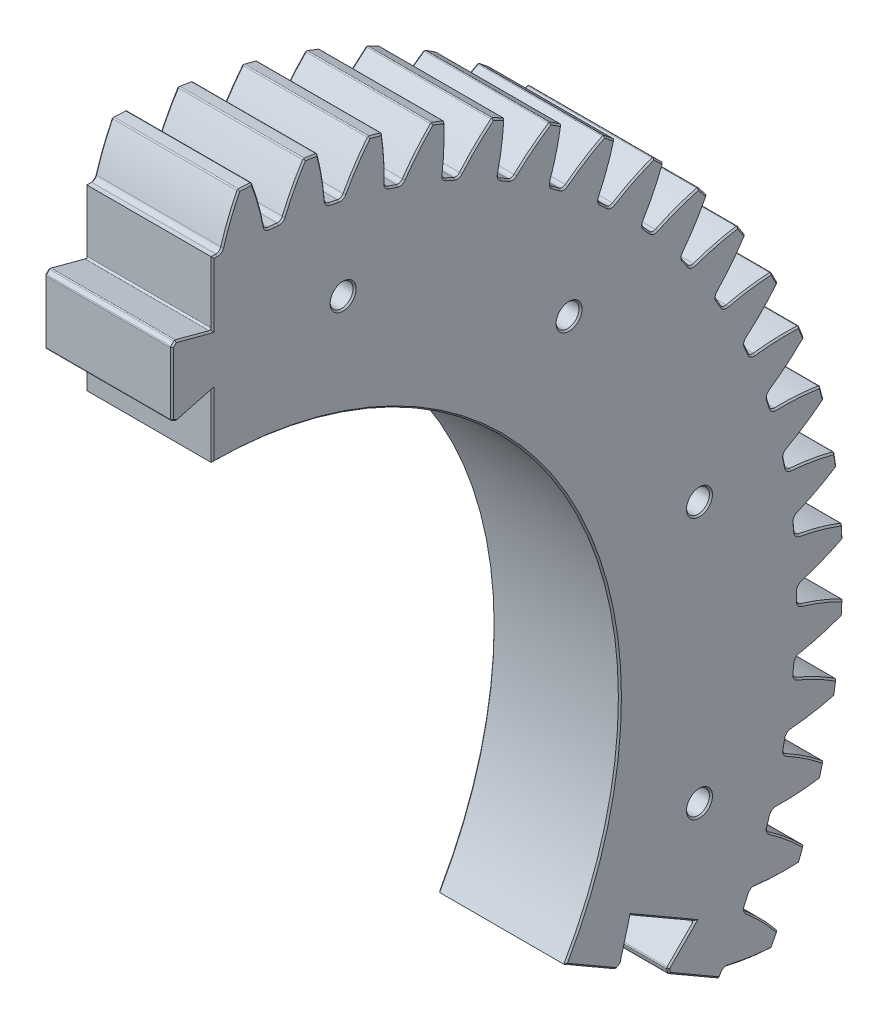
SolidWorks part; units mm, degrees
ref_plane "Plane1" through (0, 0, 0) normal (0, 0, 1) x (1, 0, 0)
ref_plane "Plane2" through (0, 0, 0) normal (0, 1, 0) x (1, 0, 0)
ref_plane "Plane3" through (0, 0, 0) normal (1, 0, 0) x (0, 0, -1)
sketch "HoldingSke" plane through (0, 0, 0) normal (0, 1, 0) x (1, 0, 0)
  line L0 (0, 0) -> (0.125, -0.2165)
  line L1 (-15, 0) -> (100, 0) construction
  line L2 (0, 0) -> (-2.1039, 2.3779)
  line L3 (0, 0) -> (-11.863, 4.5341)
  line L4 (0, 0) -> (4.318, 7.479)
  line L5 (0, 0) -> (-46.8476, -17.4728)
  line L6 (0, 0) -> (-20.7241, -13.9826)
  line L7 (-2.1039, 2.3779) -> (8.6586, 51.2059)
  line L8 (-76.2, 54.61) -> (-66.8, 54.61)
  line L9 (-71.009, 38.7566) -> (-53.1078, 45.2721)
  line L10 (-76.2, 71.12) -> (104.1128, 71.12)
  line L11 (0, 0) -> (-25, 0)
  line L12 (-76.2, 101.6) -> (-76.073, 101.6)
  line L13 (24.9733, 27.94) -> (52.9518, 28.4284)
  line L14 (24.9733, 27.94) -> (24.9743, 27.94)
  line L15 (24.9733, 27.94) -> (100.4006, 29.5858)
  line L16 (-63.627, -4) -> (-12.827, -4)
  circle A0 centre (0, 0) radius 80
  circle A1 centre (0, 0) radius 37.5
  circle A2 centre (0, 0) radius 37.5
  circle A3 centre (0, 0) radius 80
  dimension "Num_teeth" = 60
  dimension "Pitch_radius" = 180.3128
  dimension "Width" = 25
  dimension "Thickness" = 25
sketch "BasProSke" plane through (0, 0, 0) normal (0, 1, 0) x (1, 0, 0)
  line L0 (-10, 0) -> (60, 0) construction
  line L1 (0, 0) -> (0, 124)
  line L2 (0, 0) -> (25, 0)
  line L3 (25, 0) -> (25, 124)
  line L4 (25, 124) -> (0, 124)
  dimension "Thickness" = 25
  dimension "Diameter" = 248
revolve "Base-Revolve" add sketch "BasProSke" angle 360 about L0
sketch "TooCutSke" plane through (0, 0, 0) normal (1, 0, 0) x (0, 0, -1)
  line L1 (0, 0) -> (0, 107) construction
  line L2 (0, 0) -> (-3.3635, 119.9529) construction
  line L3 (0, 0) -> (-12.5569, 239.6002) construction
  line L4 (-3.3635, 119.9529) -> (-6.2785, 119.8001) construction
  arc A0 (1.6795, 114.9867) -> (-1.6795, 114.9867) centre (0, 0) ccw
  arc A1 (5.1673, 123.9177) -> (-5.1673, 123.9177) centre (0, 0) ccw
  circle A2 centre (0, 0) radius 120 construction
  circle A3 centre (0, 0) radius 112.7631 construction
  arc A4 (-1.6795, 114.9867) -> (-5.1673, 123.9177) centre (-47.9113, 102.0785) ccw
  arc A5 (5.1673, 123.9177) -> (1.6795, 114.9867) centre (47.9113, 102.0785) ccw
extrude "ToothCut" cut sketch "TooCutSke" along normal through all
fillet "Breaks" [suppressed] radius 0.08
fillet "RootFillets" [suppressed] radius 1.001
pattern_circular "TeethCuts" count 60 every 6 about axis through (-10, 0, 0) along (1, 0, 0) of "ToothCut", "RootFillets", "Breaks"
sketch "HubNeaOneSke" plane through (0, 0, 0) normal (-1, 0, 0) x (0, 0, 1)
  circle A0 centre (0, 0) radius 37.5
  dimension "Diameter" = 75
extrude "HubNearOne" [suppressed] add sketch "HubNeaOneSke" along normal blind 25.0001
sketch "HubNeaBotSke" plane through (0, 0, 0) normal (-1, 0, 0) x (0, 0, 1)
  circle A0 centre (0, 0) radius 37.5
  dimension "Diameter" = 75
extrude "HubNearBoth" [suppressed] add sketch "HubNeaBotSke" along normal blind 12.5
ref_plane "FarPln" through (25, 0, 0) normal (1, 0, 0) x (0, 0, -1)
sketch "HubFarSke" plane through (25, 0, 0) normal (1, 0, 0) x (0, 0, -1)
  circle A0 centre (0, 0) radius 37.5
  dimension "Diameter" = 75
extrude "HubFar" [suppressed] add sketch "HubFarSke" along normal blind 12.5
sketch "BorSke" plane through (0, 0, 0) normal (1, 0, 0) x (0, 0, -1)
  circle A0 centre (0, 0) radius 80
  dimension "Diameter" = 160
extrude "Bore" cut sketch "BorSke" along normal mid plane 100.0001
sketch "KeySke" plane through (0, 0, 0) normal (1, 0, 0) x (0, 0, -1)
  line L0 (-20, 0) -> (-20, 89.4)
  line L1 (-20, 89.4) -> (20, 89.4)
  line L2 (20, 89.4) -> (20, 0)
  line L3 (0, 0) -> (0, 34) construction
  line L4 (-20, 0) -> (20, 0)
  dimension "Width" = 40
extrude "Keyway" [suppressed] cut sketch "KeySke" along normal mid plane 100.0001
pattern_circular "Keyway2" [suppressed] count 2 every 90 about axis through (-10, 0, 0) along (1, 0, 0)
sketch "Esquisse2" plane through (25, 0, 0) normal (1, 0, 0) x (0, 0, -1)
  line L0 (0, 0) -> (0, 145.329) construction
  line L1 (0, 0) -> (-133.1237, -76.859) construction
  line L2 (0, 0) -> (160.6659, -92.7605) construction
  line L3 (0, 114.999) -> (0, 102.5)
  line L4 (0, 102.5) -> (-8, 104.6436)
  line L5 (-8, 104.6436) -> (-8, 90.3564)
  line L6 (-8, 90.3564) -> (0, 92.5)
  line L10 (0, 0) -> (80.0207, -46.2)
  line L11 (80.0207, -46.2) -> (82.2045, -38.05)
  line L12 (82.2045, -38.05) -> (94.8204, -45.3338)
  line L13 (94.8204, -45.3338) -> (88.8542, -51.3)
  line L14 (88.8542, -51.3) -> (114.7231, -66.2354)
  line L15 (114.7231, -66.2354) -> (38.3008, -156.6616)
  line L16 (38.3008, -156.6616) -> (-106.3416, -136.6523)
  line L17 (-106.3416, -136.6523) -> (-159.8958, -12.4772)
  line L18 (-159.8958, -12.4772) -> (-109.243, 114.999)
  line L19 (-109.243, 114.999) -> (0, 136.3991)
  line L20 (0, 136.3991) -> (0, 114.999)
  line L21 (0, 92.5) -> (0, 0)
  arc A0 (1.6795, 114.9867) -> (-1.6795, 114.9867) centre (0, 0) ccw construction
  dimension "D12" = 8
  dimension "D1" = 120
  dimension "D2" = 120
  dimension "D3" = 75
  dimension "D4" = 92.5
  dimension "D5" = 10
  dimension "D6" = 75
  dimension "D7" = 10.2
  dimension "D8" = 75
  dimension "D9" = 75
  dimension "D10" = 8.15
  dimension "D11" = 92.4
extrude "Enlèv. mat.-Extru.1" cut sketch "Esquisse2" against normal through all
sketch "Esquisse3" plane through (25, 0, 0) normal (1, 0, 0) x (0, 0, -1)
  line L0 (25.6231, 95.6267) -> (0, 0) construction
  line L1 (0, 0) -> (70.0036, 70.0036) construction
  line L2 (95.6267, 25.6231) -> (0, 0) construction
  line L3 (0, 0) -> (95.6267, -25.6231) construction
  line L7 (0, 80) -> (0, 92.5) construction
  circle A1 centre (25.6231, 95.6267) radius 2.25
  circle A2 centre (70.0036, 70.0036) radius 2.25
  circle A3 centre (95.6267, 25.6231) radius 2.25
  circle A4 centre (95.6267, -25.6231) radius 2.25
  arc A6 (69.282, -40) -> (0, 80) centre (0, 0) ccw construction
  dimension "D1" = 4.5
  dimension "D2" = 4.5
  dimension "D3" = 4.5
  dimension "D4" = 4.5
  dimension "D5" = 99
  dimension "D6" = 99
  dimension "D7" = 99
  dimension "D8" = 99
  dimension "D9" = 30
  dimension "D10" = 30
  dimension "D11" = 30
  dimension "D12" = 15
extrude "Enlèv. mat.-Extru.2" cut sketch "Esquisse3" against normal through all
fillet "Congé1" radius 1 40 edges at (12.5, 114.9867, -1.6795) (12.5, 114.5324, -10.3491) (12.5, 114.1813, -13.6897) (12.5, 112.8232, -22.2643) (12.5, 112.1248, -25.5499) (12.5, 109.8779, -33.9355) (12.5, 108.8399, -37.1302) (12.5, 105.7287, -45.235) (12.5, 104.3625, -48.3036) (12.5, 100.4212, -56.0389) (12.5, 98.7417, -58.9479) (12.5, 94.0134, -66.2288) (12.5, 92.039, -68.9463) (12.5, 86.5756, -75.693) (12.5, 84.328, -78.1893) (12.5, 78.1893, -84.328) (12.5, 75.693, -86.5756) (12.5, 68.9463, -92.039) (12.5, 66.2288, -94.0134) (12.5, 58.9479, -98.7417) (12.5, 56.0389, -100.4212) (12.5, 48.3036, -104.3625) (12.5, 45.235, -105.7287) (12.5, 37.1302, -108.8399) (12.5, 33.9355, -109.8779) (12.5, 25.5499, -112.1248) (12.5, 22.2643, -112.8232) (12.5, 13.6897, -114.1813) (12.5, 10.3491, -114.5324) (12.5, 1.6795, -114.9867) (12.5, -1.6795, -114.9867) (12.5, -10.3491, -114.5324) (12.5, -13.6897, -114.1813) (12.5, -22.2643, -112.8232) (12.5, -25.5499, -112.1248) (12.5, -33.9355, -109.8779) (12.5, -37.1302, -108.8399) (12.5, -56.0389, -100.4212) (12.5, -45.235, -105.7287) (12.5, -48.3036, -104.3625)
chamfer "Chanfrein1" distance 0.3 angle 45 272 edges at (25, 86.25, 0) (25, 91.4282, 4) (25, 97.5, 8) (25, 103.5718, 4) (25, 108.7495, 0) (25, 114.9981, -0.4606) (25, 115.1916, -1.5242) (25, 119.8771, -3.3332) (25, 123.8301, -6.4897) (25, 119.5689, -9.2157) (25, 114.7199, -10.5249) (25, 114.369, -12.0207) (25, 114.4013, -13.5567) (25, 118.872, -15.8455) (25, 122.4734, -19.3979) (25, 117.9505, -21.6635) (25, 112.9913, -22.4588) (25, 112.486, -23.9096) (25, 112.3575, -25.4406) (25, 116.5645, -28.1842) (25, 119.7748, -32.0936) (25, 115.0399, -33.874) (25, 110.0248, -34.1465) (25, 109.3705, -35.5366) (25, 109.0827, -37.0458) (25, 112.9799, -40.2141) (25, 115.764, -44.4376) (25, 110.8689, -45.7134) (25, 105.8528, -45.4602) (25, 105.0568, -46.7743) (25, 104.6128, -48.2451) (25, 108.1575, -51.8034) (25, 110.4848, -56.2948) (25, 105.4832, -57.052) (25, 100.521, -56.2758) (25, 99.5921, -57.4995) (25, 98.9968, -58.9158) (25, 102.1501, -62.8252) (25, 103.9952, -67.5352) (25, 98.9418, -67.7654) (25, 94.0879, -66.4748) (25, 93.0361, -67.5947) (25, 92.2961, -68.9411) (25, 95.0235, -73.1586) (25, 96.3661, -78.0357) (25, 91.3164, -77.7364) (25, 86.624, -75.9455) (25, 85.4609, -76.9494) (25, 84.5842, -78.211) (25, 86.8558, -82.6905) (25, 87.6812, -87.6812) (25, 82.6905, -86.8558) (25, 78.211, -84.5842) (25, 76.9494, -85.4609) (25, 75.9455, -86.624) (25, 77.7364, -91.3164) (25, 78.0357, -96.3661) (25, 73.1586, -95.0235) (25, 68.9411, -92.2961) (25, 67.5947, -93.0361) (25, 66.4748, -94.0879) (25, 67.7654, -98.9418) (25, 67.5352, -103.9952) (25, 62.8252, -102.1501) (25, 58.9158, -98.9968) (25, 57.4995, -99.5921) (25, 56.2758, -100.521) (25, 57.052, -105.4832) (25, 56.2948, -110.4848) (25, 51.8034, -108.1575) (25, 48.2451, -104.6128) (25, 46.7743, -105.0568) (25, 45.4602, -105.8528) (25, 45.7134, -110.8689) (25, 44.4376, -115.764) (25, 40.2141, -112.9799) (25, 37.0458, -109.0827) (25, 35.5366, -109.3705) (25, 34.1465, -110.0248) (25, 33.874, -115.0399) (25, 32.0936, -119.7748) (25, 28.1842, -116.5645) (25, 25.4406, -112.3575) (25, 23.9096, -112.486) (25, 22.4588, -112.9913) (25, 21.6635, -117.9505) (25, 19.3979, -122.4734) (25, 15.8455, -118.872) (25, 13.5567, -114.4013) (25, 12.0207, -114.369) (25, 10.5249, -114.7199) (25, 9.2157, -119.5689) (25, 6.4897, -123.8301) (25, 3.3332, -119.8771) (25, 1.5242, -115.1916) (25, 0, -114.999) (25, -1.5242, -115.1916) (25, -3.3332, -119.8771) (25, -6.4897, -123.8301) (25, -9.2157, -119.5689) (25, -10.5249, -114.7199) (25, -12.0207, -114.369) (25, -13.5567, -114.4013) (25, -15.8455, -118.872) (25, -19.3979, -122.4734) (25, -21.6635, -117.9505) (25, -22.4588, -112.9913) (25, -23.9096, -112.486) (25, -25.4406, -112.3575) (25, -28.1842, -116.5645) (25, -32.0936, -119.7748) (25, -33.874, -115.0399) (25, -34.1465, -110.0248) (25, -35.5366, -109.3705) (25, -37.0458, -109.0827) (25, -40.2141, -112.9799) (25, -44.4376, -115.764) (25, -45.7134, -110.8689) (25, -45.4602, -105.8528) (25, -46.7743, -105.0568) (25, -48.2451, -104.6128) (25, -51.8034, -108.1575) (25, -56.2948, -110.4848) (25, -57.052, -105.4832) (25, -56.2758, -100.521) (25, -57.1002, -99.8215) (25, -54.3998, -94.2231) (25, -48.3169, -91.8373) (25, -41.6919, -88.5125) (25, -42.125, -81.1126) (25, -43.1, -74.6514) (25, 40, -69.282) (25, -25.6231, -97.8767) (25, 25.6231, -97.8767) (25, 70.0036, -72.2536) (25, 95.6267, -27.8731) (0, -41.6919, -88.5125) (0, -48.3169, -91.8373) (0, -54.3998, -94.2231) (0, -57.1002, -99.8215) (0, -56.2758, -100.521) (0, -57.052, -105.4832) (0, -56.2948, -110.4848) (0, -51.8034, -108.1575) (0, -48.2451, -104.6128) (0, -46.7743, -105.0568) (0, -45.4602, -105.8528) (0, -45.7134, -110.8689) (0, -44.4376, -115.764) (0, -40.2141, -112.9799) (0, -37.0458, -109.0827) (0, -35.5366, -109.3705) (0, -34.1465, -110.0248) (0, -33.874, -115.0399) (0, -32.0936, -119.7748) (0, -28.1842, -116.5645) (0, -25.4406, -112.3575) (0, -23.9096, -112.486) (0, -22.4588, -112.9913) (0, -21.6635, -117.9505) (0, -19.3979, -122.4734) (0, -15.8455, -118.872) (0, -13.5567, -114.4013) (0, -12.0207, -114.369) (0, -10.5249, -114.7199) (0, -9.2157, -119.5689) (0, -6.4897, -123.8301) (0, -3.3332, -119.8771) (0, -1.5242, -115.1916) (0, 0, -114.999) (0, 1.5242, -115.1916) (0, 3.3332, -119.8771) (0, 6.4897, -123.8301) (0, 9.2157, -119.5689) (0, 10.5249, -114.7199) (0, 12.0207, -114.369) (0, 13.5567, -114.4013) (0, 15.8455, -118.872) (0, 19.3979, -122.4734) (0, 21.6635, -117.9505) (0, 22.4588, -112.9913) (0, 23.9096, -112.486) (0, 25.4406, -112.3575) (0, 28.1842, -116.5645) (0, 32.0936, -119.7748) (0, 33.874, -115.0399) (0, 34.1465, -110.0248) (0, 35.5366, -109.3705) (0, 37.0458, -109.0827) (0, 40.2141, -112.9799) (0, 44.4376, -115.764) (0, 45.7134, -110.8689) (0, 45.4602, -105.8528) (0, 46.7743, -105.0568) (0, 48.2451, -104.6128) (0, 51.8034, -108.1575) (0, 56.2948, -110.4848) (0, 57.052, -105.4832) (0, 56.2758, -100.521) (0, 57.4995, -99.5921) (0, 58.9158, -98.9968) (0, 62.8252, -102.1501) (0, 67.5352, -103.9952) (0, 67.7654, -98.9418) (0, 66.4748, -94.0879) (0, 67.5947, -93.0361) (0, 68.9411, -92.2961) (0, 73.1586, -95.0235) (0, 78.0357, -96.3661) (0, 77.7364, -91.3164) (0, 75.9455, -86.624) (0, 76.9494, -85.4609) (0, 78.211, -84.5842) (0, 82.6905, -86.8558) (0, 87.6812, -87.6812) (0, 86.8558, -82.6905) (0, 84.5842, -78.211) (0, 85.4609, -76.9494) (0, 86.624, -75.9455) (0, 91.3164, -77.7364) (0, 96.3661, -78.0357) (0, 95.0235, -73.1586) (0, 92.2961, -68.9411) (0, 93.0361, -67.5947) (0, 94.0879, -66.4748) (0, 98.9418, -67.7654) (0, 103.9952, -67.5352) (0, 102.1501, -62.8252) (0, 98.9968, -58.9158) (0, 99.5921, -57.4995) (0, 100.521, -56.2758) (0, 105.4832, -57.052) (0, 110.4848, -56.2948) (0, 108.1575, -51.8034) (0, 104.6128, -48.2451) (0, 105.0568, -46.7743) (0, 105.8528, -45.4602) (0, 110.8689, -45.7134) (0, 115.764, -44.4376) (0, 112.9799, -40.2141) (0, 109.0827, -37.0458) (0, 109.3705, -35.5366) (0, 110.0248, -34.1465) (0, 115.0399, -33.874) (0, 119.7748, -32.0936) (0, 116.5645, -28.1842) (0, 112.3575, -25.4406) (0, 112.486, -23.9096) (0, 112.9913, -22.4588) (0, 117.9505, -21.6635) (0, 122.4734, -19.3979) (0, 118.872, -15.8455) (0, 114.4013, -13.5567) (0, 114.369, -12.0207) (0, 114.7199, -10.5249) (0, 119.5689, -9.2157) (0, 123.8301, -6.4897) (0, 119.8771, -3.3332) (0, 115.1916, -1.5242) (0, 114.9981, -0.4606) (0, 108.7495, 0) (0, 103.5718, 4) (0, 97.5, 8) (0, 91.4282, 4) (0, 86.25, 0) (0, 40, -69.282) (0, -43.1, -74.6514) (0, -42.125, -81.1126) (0, -25.6231, -97.8767) (0, 25.6231, -97.8767) (0, 70.0036, -72.2536) (0, 95.6267, -27.8731)
sketch "Esquisse4" plane through (0, 0, 0) normal (-1, 0, 0) x (0, 0, 1)
  circle A0 centre (-95.6267, -25.6231) radius 6.75
  circle A1 centre (-95.6267, 25.6231) radius 6.75
  circle A2 centre (-70.0036, 70.0036) radius 6.75
  circle A3 centre (-25.6231, 95.6267) radius 6.75
  dimension "D1" = 13.5
  dimension "D2" = 13.5
  dimension "D3" = 13.5
  dimension "D4" = 13.5
extrude "Enlèv. mat.-Extru.3" cut sketch "Esquisse4" against normal blind 5.2
chamfer "Chanfrein2" distance 0.3 angle 45 4 edges at (0, 95.6267, -18.8731) (0, 70.0036, -63.2536) (0, 25.6231, -88.8767) (0, -25.6231, -88.8767)
chamfer "Chanfrein3" distance 1 angle 45 4 edges at (12.5, -46.2, -80.0207) (12.5, -51.3, -88.8542) (12.5, 90.3564, 8) (12.5, 104.6436, 8)
fillet "Congé2" radius 0.3 12 edges at (12.5, -45.7918, -79.3136) (12.5, -45.2341, -80.2796) (12.5, -38.05, -82.2045) (12.5, -45.3338, -94.8204) (12.5, -50.7226, -89.4316) (12.5, -51.8, -89.7202) (12.5, 104.4323, 7.2113) (12.5, 103.6436, 8) (12.5, 91.1729, 8) (12.5, 90.6152, 7.0341) (12.5, 92.5, 0) (12.5, 102.5, 0)
chamfer "Chanfrein4" distance 0.3 angle 45 8 edges at (0, -51.2237, -89.5658) (25, -51.2237, -89.5658) (0, -45.5324, -79.7629) (25, -45.5324, -79.7629) (25, 90.9135, 7.5507) (25, 104.0655, 7.5781) (0, 90.9135, 7.5507) (0, 104.0655, 7.5781)
fillet "Congé3" radius 0.3 40 edges at (12.5, 123.8928, -5.1546) (12.5, 123.7529, -7.824) (12.5, 122.6753, -18.0767) (12.5, 122.2572, -20.7168) (12.5, 120.1138, -30.8007) (12.5, 119.4219, -33.3827) (12.5, 116.2362, -43.1873) (12.5, 115.2783, -45.6828) (12.5, 111.0852, -55.1007) (12.5, 109.8716, -57.4824) (12.5, 104.717, -66.4104) (12.5, 103.2612, -68.6522) (12.5, 97.2016, -76.9925) (12.5, 95.5194, -79.0699) (12.5, 88.6212, -86.7311) (12.5, 86.7311, -88.6212) (12.5, 79.0699, -95.5194) (12.5, 76.9925, -97.2016) (12.5, 68.6522, -103.2612) (12.5, 66.4104, -104.717) (12.5, 57.4824, -109.8716) (12.5, 55.1007, -111.0852) (12.5, 45.6828, -115.2783) (12.5, 43.1873, -116.2362) (12.5, 33.3827, -119.4219) (12.5, 30.8007, -120.1138) (12.5, 20.7168, -122.2572) (12.5, 18.0767, -122.6753) (12.5, 7.824, -123.7529) (12.5, 5.1546, -123.8928) (12.5, -5.1546, -123.8928) (12.5, -7.824, -123.7529) (12.5, -18.0767, -122.6753) (12.5, -20.7168, -122.2572) (12.5, -30.8007, -120.1138) (12.5, -33.3827, -119.4219) (12.5, -43.1873, -116.2362) (12.5, -45.6828, -115.2783) (12.5, -55.1007, -111.0852) (12.5, -57.4824, -109.8716)
equation "' \"Module@HoldingSke\" = 6.35"
equation "' \"Num_teeth@HoldingSke\" = 12"
equation "' \"Ap@HoldingSke\" =  20"
equation "' \"Ap@HoldingSke\" = 20"
equation "' \"Width@HoldingSke\" = 0.5 * 25.4"
equation "' \"Hub_dia@HoldingSke\"= 1 * 25.4"
equation "' \"Hub_dia@HoldingSke\" = 1 * 25.4"
equation "' \"Overall_len@HoldingSke\" = 1.0 * 25.4"
equation "' \"Bore@HoldingSke\" = 0.75 * 25.4"
equation "' \"T_dim@HoldingSke\" = 0.1 * 25.4"
equation "' \"Width@KeySke\" = 0.25 * 25.4"
equation "' \"Show_teeth@HoldingSke\" = 13"
equation "' \"Backlash@HoldingSke\" = 0.009 * 25.4"
equation "' \"Addendum_fac@HoldingSke\" = 1.0"
equation "' \"Dedendum_fac@HoldingSke\" = 1.25"
equation "' \"Dedendum_add@HoldingSke\" = 0.00005 * 25.4"
equation "' \"Clearance_fac@HoldingSke\" = 0.25"
equation "\"Pitch@HoldingSke\" = 1 / \"Module@HoldingSke\""
equation "\"Overcut_dia@TooCutSke\" = (\"Num_teeth@HoldingSke\" + 2 * \"Addendum_fac@HoldingSke\") / \"Pitch@HoldingSke\" + 0.002 * 25.4"
equation "\"Pitch_dia@TooCutSke\" = \"Num_teeth@HoldingSke\" / \"Pitch@HoldingSke\""
equation "\"Base_dia@TooCutSke\" = \"Num_teeth@HoldingSke\" / \"Pitch@HoldingSke\" * cos((\"Ap@HoldingSke\"  * 3.14159265 / 180))"
equation "\"Root_dia@TooCutSke\" = (\"Num_teeth@HoldingSke\" + 2) / \"Pitch@HoldingSke\" - 2 * (\"Addendum_fac@HoldingSke\" + \"Dedendum_fac@HoldingSke\") / \"Pitch@HoldingSke\" - \"Dedendum_add@HoldingSke\" * 2"
equation "\"Half_ang@TooCutSke\" = 180 / \"Num_teeth@HoldingSke\""
equation "\"Half_CT@TooCutSke\" = \"Num_teeth@HoldingSke\" / \"Pitch@HoldingSke\" * sin((3.14159265 / 2 / \"Num_teeth@HoldingSke\")) / 2 - 7 * \"Backlash@HoldingSke\" / 4"
equation "\"Flank_rad@TooCutSke\" = \"Num_teeth@HoldingSke\" / \"Pitch@HoldingSke\" / 5"
equation "\"Radius@RootFillets\" = \"Clearance_fac@HoldingSke\" / \"Pitch@HoldingSke\" + \"Dedendum_add@HoldingSke\""
equation "\"Break_rad@Breaks\" = 0.02 / \"Pitch@HoldingSke\""
equation "\"Thickness@HoldingSke\" = \"Width@HoldingSke\""
equation "\"OAL@HoldingSke\" = \"Thickness@HoldingSke\""
equation "\"MHD@HoldingSke\" = (\"Num_teeth@HoldingSke\" + 2) / \"Pitch@HoldingSke\" - 2 * (\"Addendum_fac@HoldingSke\" + \"Dedendum_fac@HoldingSke\")  / \"Pitch@HoldingSke\" - \"Dedendum_add@HoldingSke\" * 2"
equation "\"MBD@HoldingSke\" = (\"Num_teeth@HoldingSke\" + 2) / \"Pitch@HoldingSke\" - 2 * (\"Addendum_fac@HoldingSke\" + \"Dedendum_fac@HoldingSke\")  / \"Pitch@HoldingSke\" - \"Dedendum_add@HoldingSke\" * 2 - 0.002 * 25.4"
equation "\"MHD@HoldingSke\" = ((sgn( \"MHD@HoldingSke\" - \"Hub_dia@HoldingSke\" )-1)*( \"MHD@HoldingSke\" - \"Hub_dia@HoldingSke\" ))/-2+ \"Hub_dia@HoldingSke\""
equation "\"MBD@HoldingSke\" = ((sgn( \"MBD@HoldingSke\" - \"Bore@HoldingSke\" )-1)*( \"MBD@HoldingSke\" - \"Bore@HoldingSke\" ))/-2+ \"Bore@HoldingSke\""
equation "\"OAL@HoldingSke\" = ((sgn( \"OAL@HoldingSke\" - \"Overall_len@HoldingSke\" )+1)*( \"OAL@HoldingSke\" - \"Overall_len@HoldingSke\" ))/2 + \"Overall_len@HoldingSke\" + 0.000002 * 25.4"
equation "\"Num_teeth@TeethCuts\" = int( \"Show_teeth@HoldingSke\" ) + 1"
equation "\"Num_teeth@TeethCuts\" = ((sgn( \"Num_teeth@TeethCuts\" - \"Num_teeth@HoldingSke\" )-1)*( \"Num_teeth@TeethCuts\" - \"Num_teeth@HoldingSke\" ))/-2+ \"Num_teeth@HoldingSke\""
equation "\"Num_teeth@TeethCuts\" = ((sgn( \"Num_teeth@TeethCuts\" - 2.0)+1)*( \"Num_teeth@TeethCuts\" - 2.0))/2 +2.0"
equation "\"Angle@TeethCuts\" = 360.0 / \"Num_teeth@HoldingSke\""
equation "\"Diameter@BasProSke\" = (\"Num_teeth@HoldingSke\" + 2 * \"Addendum_fac@HoldingSke\") / \"Pitch@HoldingSke\""
equation "\"Thickness@BasProSke\"  = \"Thickness@HoldingSke\""
equation "' \"Fillet_rad@BasProSke\" =  \"Thickness@HoldingSke\" * 0.05"
equation "' \"Fillet_rad@BasProSke\" = \"Thickness@HoldingSke\" * 0.05"
equation "\"MHD@HoldingSke\" = ((sgn( \"MHD@HoldingSke\" - \"Root_dia@TooCutSke\" )-1)*( \"MHD@HoldingSke\" - \"Root_dia@TooCutSke\" ))/-2+ \"Root_dia@TooCutSke\""
equation "\"Diameter@HubNeaOneSke\" = \"MHD@HoldingSke\""
equation "\"Length@HubNearOne\" = \"OAL@HoldingSke\" - \"Thickness@BasProSke\""
equation "\"Diameter@HubNeaBotSke\" = \"MHD@HoldingSke\""
equation "\"Length@HubNearBoth\" = ( \"OAL@HoldingSke\" - \"Thickness@BasProSke\" ) / 2.0"
equation "\"Thickness@FarPln\" = \"Thickness@BasProSke\""
equation "\"Diameter@HubFarSke\" = \"MHD@HoldingSke\""
equation "\"Length@HubFar\" = ( \"OAL@HoldingSke\" - \"Thickness@BasProSke\" ) / 2.0"
equation "\"Diameter@BorSke\" = \"MBD@HoldingSke\""
equation "\"D1@Bore\" = \"OAL@HoldingSke\" * 2.0"
equation "\"D1@Keyway\" = \"OAL@HoldingSke\" * 2.0"
equation "\"Offset@KeySke\" = \"T_dim@HoldingSke\" + \"MBD@HoldingSke\" / 2.0"
